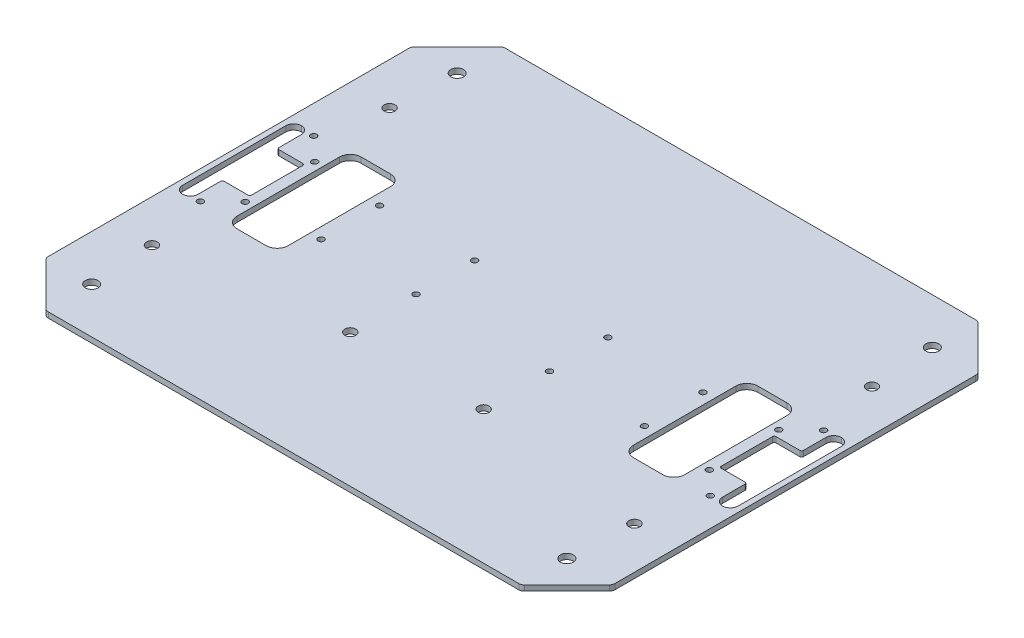
SolidWorks part; units mm, degrees
ref_plane "Plan de face" through (0, 0, 0) normal (0, 0, 1) x (1, 0, 0)
ref_plane "Plan de dessus" through (0, 0, 0) normal (0, 1, 0) x (1, 0, 0)
ref_plane "Plan de droite" through (0, 0, 0) normal (1, 0, 0) x (0, 0, -1)
sketch "Esquisse1" plane through (0, 0, 0) normal (0, 1, 0) x (1, 0, 0)
  line L0 (0, 125) -> (0, -125) construction
  line L1 (-155, 0) -> (155, 0) construction
  line L2 (-130, 125) -> (130, 125)
  line L3 (-130, -125) -> (130, -125)
  line L4 (-155, 100) -> (-155, -100)
  line L5 (155, 100) -> (155, -100)
  line L6 (-155, 100) -> (-130, 125)
  line L7 (-155, -100) -> (-130, -125)
  line L8 (130, -125) -> (155, -100)
  line L9 (130, 125) -> (155, 100)
  point P4 (0, 0)
  point P8 (0, 0)
  point P10 (0, 125)
  point P14 (0, -125)
  point P17 (-155, 0)
  point P20 (155, 0)
  dimension "D1" = 310
  dimension "D2" = 250
  dimension "D3" = 135
  dimension "D4" = 260
  dimension "D5" = 200
extrude "Boss.-Extru.1" add sketch "Esquisse1" along normal blind 3
fillet "Congé1" radius 3 8 edges at (-155, 1.5, 100) (-130, 1.5, 125) (130, 1.5, 125) (155, 1.5, 100) (155, 1.5, -100) (130, 1.5, -125) (-130, 1.5, -125) (-155, 1.5, -100)
sketch "Esquisse2" plane through (0, 3, 0) normal (0, 1, 0) x (1, 0, 0)
  line L0 (155, 0) -> (-155, 0) construction
  line L1 (-155, 98.7574) -> (-155, -98.7574) construction
  line L2 (-132, 0) -> (-132, -65) construction
  line L3 (-132, -65) -> (-155, -65) construction
  line L4 (0, 125) -> (0, -125) construction
  line L5 (-128.7574, -125) -> (128.7574, -125) construction
  circle A0 centre (-132, -65) radius 3
  circle A1 centre (-132, 65) radius 3
  circle A2 centre (132, -65) radius 3
  circle A3 centre (132, 65) radius 3
  point P6 (0, 0)
  point P18 (0, 0)
  dimension "D3" = 6
  dimension "D1" = 23
  dimension "D2" = 65
extrude "Perçage Profilé" cut sketch "Esquisse2" against normal through all
sketch "Esquisse3" plane through (0, 3, 0) normal (0, 1, 0) x (1, 0, 0)
  line L0 (-127, 19) -> (-127, -19) construction
  line L1 (155, 0) -> (-155, 0) construction
  line L2 (-155, 98.7574) -> (-155, -98.7574) construction
  line L3 (0, 125) -> (0, -125) construction
  line L4 (-128.7574, -125) -> (128.7574, -125) construction
  line L5 (-139.5, -31) -> (-139.5, 31) construction
  circle A0 centre (-127, 19) radius 1.65
  circle A1 centre (-127, -19) radius 1.65
  circle A2 centre (127, -19) radius 1.65
  circle A3 centre (127, 19) radius 1.65
  circle A4 centre (-139.5, 31) radius 1.65
  circle A5 centre (-139.5, -31) radius 1.65
  circle A6 centre (139.5, -31) radius 1.65
  circle A7 centre (139.5, 31) radius 1.65
  point P4 (-127, 0)
  point P10 (0, 0)
  point P16 (0, 0)
  point P23 (-139.5, 0)
  dimension "D2" = 3.3
  dimension "D1" = 38
  dimension "D3" = 28
  dimension "D4" = 62
  dimension "D5" = 12.5
extrude "Perçage Encodeur" cut sketch "Esquisse3" against normal through all
sketch "Esquisse4" plane through (0, 3, 0) normal (0, 1, 0) x (1, 0, 0)
  line L0 (155, 0) -> (-155, 0) construction
  line L1 (143.5, -15) -> (129.5, -15)
  line L2 (-128.5, -14) -> (-128.5, 14)
  line L4 (-129.5, 15) -> (-143.5, 15)
  line L5 (-143.5, 15) -> (-143.5, 32.5)
  line L6 (-143.5, 32.5) -> (-152, 32.5)
  line L7 (-152, 32.5) -> (-152, -32.5)
  line L8 (-152, -32.5) -> (-143.5, -32.5)
  line L9 (-143.5, -32.5) -> (-143.5, -15)
  line L10 (-143.5, -15) -> (-129.5, -15)
  line L12 (-143.5, 15) -> (-143.5, -15) construction
  line L13 (143.5, -32.5) -> (143.5, -15)
  line L14 (0, 125) -> (0, -125) construction
  line L15 (-128.7574, -125) -> (128.7574, -125) construction
  line L16 (152, -32.5) -> (143.5, -32.5)
  line L27 (-155, 98.7574) -> (-155, -98.7574) construction
  line L28 (152, 32.5) -> (152, -32.5)
  line L29 (143.5, 32.5) -> (152, 32.5)
  line L30 (143.5, 15) -> (143.5, 32.5)
  line L31 (129.5, 15) -> (143.5, 15)
  line L32 (128.5, -14) -> (128.5, 14)
  arc A0 (-128.5, -14) -> (-129.5, -15) centre (-129.5, -14) cw
  arc A1 (-128.5, 14) -> (-129.5, 15) centre (-129.5, 14) ccw
  arc A2 (128.5, 14) -> (129.5, 15) centre (129.5, 14) cw
  arc A3 (128.5, -14) -> (129.5, -15) centre (129.5, -14) ccw
  point P6 (0, 0)
  point P10 (-128.5, 0)
  point P19 (-143.5, 0)
  point P25 (0, 0)
  point P28 (-128.5, 15)
  point P32 (-152, 0)
  point P45 (128.5, 15)
  point P46 (128.5, 0)
  dimension "D2" = 1
  dimension "D1" = 15
  dimension "D3" = 8.5
  dimension "D4" = 65
  dimension "D5" = 30
  dimension "D6" = 3
extrude "Poche Roue Encodeuse" cut sketch "Esquisse4" against normal through all
fillet "Congé4" radius 1 4 edges at (143.5, 1.5, 15) (143.5, 1.5, -15) (-143.5, 1.5, 15) (-143.5, 1.5, -15)
fillet "Congé2" radius 4.25 4 edges at (152, 1.5, 32.5) (152, 1.5, -32.5) (-152, 1.5, 32.5) (-152, 1.5, -32.5)
fillet "Congé3" radius 4.25 4 edges at (143.5, 1.5, 32.5) (143.5, 1.5, -32.5) (-143.5, 1.5, 32.5) (-143.5, 1.5, -32.5)
sketch "Esquisse5" plane through (0, 3, 0) normal (0, 1, 0) x (1, 0, 0)
  line L0 (0, 125) -> (0, -125) construction
  line L1 (128.7574, 125) -> (-128.7574, 125) construction
  line L2 (-128.7574, -125) -> (128.7574, -125) construction
  line L3 (-155, 0) -> (155, 0) construction
  line L4 (-155, 98.7574) -> (-155, -98.7574) construction
  line L5 (155, -98.7574) -> (155, 98.7574) construction
  line L7 (-36.5, 16) -> (-88.5, 16) construction
  line L8 (-36.5, 16) -> (-36.5, -16) construction
  line L9 (-36.5, -16) -> (-88.5, -16) construction
  line L10 (-88.5, 16) -> (-88.5, -16) construction
  circle A0 centre (-88.5, 16) radius 1.65
  circle A1 centre (-88.5, -16) radius 1.65
  circle A2 centre (-36.5, -16) radius 1.65
  circle A3 centre (-36.5, 16) radius 1.65
  circle A4 centre (36.5, 16) radius 1.65
  circle A5 centre (36.5, -16) radius 1.65
  circle A6 centre (88.5, -16) radius 1.65
  circle A7 centre (88.5, 16) radius 1.65
  point P16 (-36.5, 0)
  dimension "D4" = 3.3
  dimension "D1" = 32
  dimension "D2" = 52
  dimension "D3" = 88.5
extrude "Perçage Bloc Moteur" cut sketch "Esquisse5" against normal through all
sketch "Esquisse6" plane through (0, 3, 0) normal (0, 1, 0) x (1, 0, 0)
  line L0 (-88.5, 16) -> (-88.5, -16) construction
  line L1 (-122.5, 34) -> (-94.5, 34)
  line L2 (-122.5, 34) -> (-122.5, -34)
  line L3 (-122.5, -34) -> (-94.5, -34)
  line L4 (-94.5, 34) -> (-94.5, -34)
  line L5 (-94.5, 0) -> (-88.5, 0) construction
  line L6 (0, 125) -> (0, -125) construction
  line L7 (-128.7574, -125) -> (128.7574, -125) construction
  line L8 (122.5, -34) -> (94.5, -34)
  line L9 (94.5, 34) -> (94.5, -34)
  line L10 (122.5, 34) -> (122.5, -34)
  line L11 (122.5, 34) -> (94.5, 34)
  point P16 (0, 0)
  dimension "D1" = 28
  dimension "D2" = 6
  dimension "D3" = 68
extrude "Poche Roue Motrice" cut sketch "Esquisse6" against normal through all
sketch "Esquisse7" plane through (0, 3, 0) normal (0, 1, 0) x (1, 0, 0)
  line L0 (-155, 98.7574) -> (-155, -98.7574) construction
  line L1 (128.7574, 125) -> (-128.7574, 125) construction
  line L2 (0, 125) -> (0, -125) construction
  line L3 (-128.7574, -125) -> (128.7574, -125) construction
  line L4 (-155, 0) -> (155, 0) construction
  line L5 (155, -98.7574) -> (155, 98.7574) construction
  circle A0 centre (-130, 100) radius 3.5
  circle A1 centre (-130, -100) radius 3.5
  circle A2 centre (130, -100) radius 3.5
  circle A3 centre (130, 100) radius 3.5
  point P12 (0, 0)
  point P18 (0, 0)
  dimension "D1" = 7
  dimension "D2" = 25
  dimension "D3" = 25
extrude "Perçage Patin" cut sketch "Esquisse7" against normal through all
sketch "Esquisse8" plane through (0, 3, 0) normal (0, 1, 0) x (1, 0, 0)
  line L0 (0, -125) -> (0, -52) construction
  line L1 (-128.7574, -125) -> (128.7574, -125) construction
  line L2 (36.5, -52) -> (-36.5, -52) construction
  circle A0 centre (-36.5, -52) radius 3
  circle A1 centre (36.5, -52) radius 3
  point P8 (0, -52)
  dimension "D3" = 6
  dimension "D1" = 73
  dimension "D2" = 73
extrude "Enlèv. mat.-Extru.1" cut sketch "Esquisse8" against normal through all
fillet "Congé5" radius 6 8 edges at (94.5, 1.5, 34) (122.5, 1.5, 34) (122.5, 1.5, -34) (94.5, 1.5, -34) (-122.5, 1.5, 34) (-94.5, 1.5, 34) (-94.5, 1.5, -34) (-122.5, 1.5, -34)
